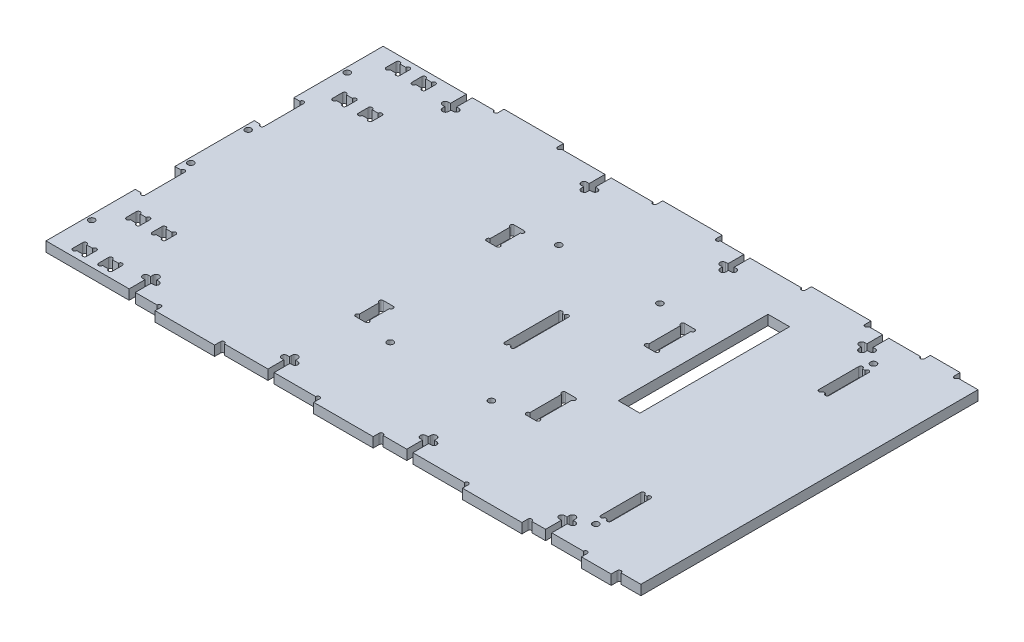
SolidWorks part; units mm, degrees
ref_plane "정면" through (0, 0, 0) normal (0, 0, 1) x (1, 0, 0)
ref_plane "윗면" through (0, 0, 0) normal (0, 1, 0) x (1, 0, 0)
ref_plane "우측면" through (0, 0, 0) normal (1, 0, 0) x (0, 0, -1)
sketch "스케치1" plane through (0, 0, 0) normal (0, 1, 0) x (1, 0, 0)
  line L1 (0, 0) -> (300, 0)
  line L2 (0, 0) -> (0, 170)
  line L3 (0, 170) -> (300, 170)
  line L4 (300, 0) -> (300, 170)
  dimension "D1" = 170
  dimension "D2" = 300
extrude "보스-돌출1" add sketch "스케치1" along normal blind 5
sketch "스케치2" plane through (0, 0, 0) normal (0, -1, 0) x (1, 0, 0)
  line L0 (159.9, -71.5) -> (159.9, 0) construction
  line L1 (159.9, -71.5) -> (165.1, -71.5)
  line L2 (159.9, -71.5) -> (159.9, -98.5)
  line L3 (159.9, -98.5) -> (165.1, -98.5)
  line L4 (165.1, -71.5) -> (165.1, -98.5)
  line L5 (0, 0) -> (300, 0) construction
  line L6 (159.9, -98.5) -> (159.9, -170) construction
  line L7 (300, -170) -> (0, -170) construction
  line L10 (300, 0) -> (300, -170) construction
  line L11 (259.8, 0) -> (259.8, -20) construction
  line L12 (259.8, -20) -> (265, -20)
  line L13 (259.8, -20) -> (259.8, -40)
  line L14 (259.8, -40) -> (265, -40)
  line L15 (265, -20) -> (265, -40)
  line L16 (259.8, -130) -> (265, -130)
  line L17 (259.8, -130) -> (259.8, -150)
  line L18 (259.8, -150) -> (265, -150)
  line L19 (265, -130) -> (265, -150)
  line L20 (259.8, -40) -> (259.8, -130) construction
  line L21 (259.8, -150) -> (259.8, -170) construction
  line L22 (265, -130) -> (265, -40) construction
  dimension "D1" = 27
  dimension "D2" = 140.1
  dimension "D3" = 5.2
  dimension "D4" = 20
  dimension "D5" = 20
  dimension "D6" = 40.2
  dimension "D7" = 5.2
extrude "컷-돌출1" cut sketch "스케치2" against normal blind 10
sketch "스케치3" plane through (0, 5, 0) normal (0, 1, 0) x (1, 0, 0)
  line L0 (183.65, 42.5) -> (180.55, 42.5) construction
  line L1 (183.65, 40) -> (183.65, 45) construction
  line L2 (180.55, 40) -> (180.55, 45) construction
  line L3 (180.55, 42.5) -> (132.65, 42.5) construction
  line L4 (132.65, 40) -> (132.65, 45) construction
  line L5 (132.65, 42.5) -> (129.55, 42.5) construction
  line L6 (129.55, 40) -> (129.55, 45) construction
  line L7 (183.65, 127.5) -> (180.55, 127.5) construction
  line L8 (183.65, 125) -> (183.65, 130) construction
  line L9 (180.55, 125) -> (180.55, 130) construction
  line L10 (180.55, 127.5) -> (132.65, 127.5) construction
  line L11 (132.65, 125) -> (132.65, 130) construction
  line L12 (132.65, 127.5) -> (129.55, 127.5) construction
  line L13 (129.55, 125) -> (129.55, 130) construction
  line L15 (2.5, 101) -> (2.5, 97.9) construction
  line L17 (5, 101) -> (0, 101) construction
  line L18 (262.3, 16.55) -> (262.3, 13.45) construction
  line L19 (264.8, 16.55) -> (259.8, 16.55) construction
  line L20 (264.8, 13.45) -> (259.8, 13.45) construction
  line L25 (262.3, 156.55) -> (262.3, 153.45) construction
  line L26 (264.8, 156.55) -> (259.8, 156.55) construction
  line L27 (264.8, 153.45) -> (259.8, 153.45) construction
  line L28 (5, 97.9) -> (0, 97.9) construction
  line L31 (2.5, 151) -> (2.5, 147.9) construction
  line L34 (2.5, 22.1) -> (2.5, 19) construction
  line L35 (5, 22.1) -> (0, 22.1) construction
  line L36 (5, 19) -> (0, 19) construction
  line L37 (2.5, 72.1) -> (2.5, 69) construction
  line L38 (5, 72.1) -> (0, 72.1) construction
  line L39 (5, 69) -> (0, 69) construction
  line L40 (5, 151) -> (0, 151) construction
  line L41 (5, 147.9) -> (0, 147.9) construction
  circle A0 centre (131.1, 127.5) radius 1.55
  circle A1 centre (182.1, 127.5) radius 1.55
  circle A2 centre (182.1, 42.5) radius 1.55
  circle A3 centre (131.1, 42.5) radius 1.55
  circle A4 centre (2.5, 70.55) radius 1.55
  circle A5 centre (2.5, 20.55) radius 1.55
  circle A6 centre (2.5, 99.45) radius 1.55
  circle A7 centre (2.5, 149.45) radius 1.55
  circle A8 centre (262.3, 155) radius 1.55
  circle A10 centre (262.3, 15) radius 1.55
  dimension "D1" = 3.1
extrude "컷-돌출2" cut sketch "스케치3" against normal blind 10
sketch "스케치4" plane through (0, 0, 0) normal (0, -1, 0) x (1, 0, 0)
  line L1 (0, -125) -> (5, -125)
  line L2 (0, -125) -> (0, -105)
  line L3 (0, -105) -> (5, -105)
  line L4 (5, -125) -> (5, -105)
  line L5 (0, -65) -> (5, -65)
  line L6 (0, -65) -> (0, -45)
  line L7 (0, -45) -> (5, -45)
  line L8 (5, -65) -> (5, -45)
extrude "컷-돌출3" cut sketch "스케치4" against normal blind 5
sketch "스케치5" plane through (0, 0, 0) normal (0, -1, 0) x (1, 0, 0)
  line L2 (5, -45) -> (0, -45) construction
  line L3 (0, -65) -> (5, -65) construction
  line L4 (5, -105) -> (0, -105) construction
  line L5 (0, -125) -> (5, -125) construction
  line L6 (159.9, -98.5) -> (165.1, -98.5) construction
  line L7 (165.1, -71.5) -> (159.9, -71.5) construction
  line L8 (265, -20) -> (259.8, -20) construction
  line L9 (259.8, -40) -> (265, -40) construction
  line L10 (265, -130) -> (259.8, -130) construction
  line L11 (259.8, -150) -> (265, -150) construction
  circle A1 centre (4, -45) radius 1
  circle A2 centre (4, -65) radius 1
  circle A5 centre (4, -105) radius 1
  circle A6 centre (4, -125) radius 1
  circle A8 centre (164.1, -98.5) radius 1
  circle A9 centre (160.9, -98.5) radius 1
  circle A10 centre (164.1, -71.5) radius 1
  circle A11 centre (160.9, -71.5) radius 1
  circle A12 centre (264, -20) radius 1
  circle A13 centre (260.8, -20) radius 1
  circle A14 centre (264, -40) radius 1
  circle A15 centre (260.8, -40) radius 1
  circle A16 centre (264, -130) radius 1
  circle A17 centre (260.8, -130) radius 1
  circle A18 centre (264, -150) radius 1
  circle A19 centre (260.8, -150) radius 1
  dimension "D1" = 2
extrude "컷-돌출4" cut sketch "스케치5" against normal blind 10
sketch "스케치8" plane through (0, 0, 0) normal (0, -1, 0) x (1, 0, 0)
  line L0 (0, 0) -> (300, 0) construction
  line L1 (58, 0) -> (88, 0)
  line L2 (58, 0) -> (58, 3)
  line L3 (58, 3) -> (88, 3)
  line L4 (88, 0) -> (88, 3)
  line L5 (0, 3) -> (58, 3) construction
  line L6 (0, 0) -> (300, 0) construction
  line L7 (138, 3) -> (168, 3)
  line L8 (138, 3) -> (138, 0)
  line L9 (138, 0) -> (168, 0)
  line L10 (168, 3) -> (168, 0)
  line L11 (0, 0) -> (300, 0) construction
  line L12 (213, 3) -> (243, 3)
  line L13 (213, 3) -> (213, 0)
  line L14 (213, 0) -> (243, 0)
  line L15 (243, 3) -> (243, 0)
  line L16 (0, 0) -> (300, 0) construction
  line L17 (273, 3) -> (288, 3)
  line L18 (273, 3) -> (273, 0)
  line L19 (273, 0) -> (288, 0)
  line L20 (288, 3) -> (288, 0)
  line L21 (300, 0) -> (300, -170) construction
  line L22 (0, -85) -> (300, -85) construction
  line L23 (0, -105) -> (0, -65) construction
  line L24 (288, -173) -> (288, -170)
  line L25 (273, -170) -> (288, -170)
  line L26 (273, -173) -> (273, -170)
  line L27 (273, -173) -> (288, -173)
  line L28 (243, -173) -> (243, -170)
  line L29 (213, -170) -> (243, -170)
  line L30 (213, -173) -> (213, -170)
  line L31 (213, -173) -> (243, -173)
  line L32 (168, -173) -> (168, -170)
  line L33 (138, -170) -> (168, -170)
  line L34 (138, -173) -> (138, -170)
  line L35 (138, -173) -> (168, -173)
  line L36 (88, -170) -> (88, -173)
  line L37 (58, -173) -> (88, -173)
  line L38 (58, -170) -> (58, -173)
  line L39 (58, -170) -> (88, -170)
  dimension "D1" = 12
  dimension "D2" = 15
  dimension "D3" = 30
  dimension "D4" = 30
  dimension "D5" = 45
  dimension "D6" = 30
  dimension "D7" = 50
  dimension "D8" = 30
extrude "보스-돌출2" add sketch "스케치8" against normal blind 5
sketch "스케치9" plane through (0, 0, 0) normal (0, -1, 0) x (1, 0, 0)
  line L0 (0, 0) -> (58, 0) construction
  line L1 (88, 0) -> (138, 0) construction
  line L2 (88, 0) -> (138, 0) construction
  line L3 (168, 0) -> (213, 0) construction
  line L4 (168, 0) -> (213, 0) construction
  line L5 (243, 0) -> (273, 0) construction
  line L6 (243, 0) -> (273, 0) construction
  line L7 (288, 0) -> (300, 0) construction
  line L8 (0, -85) -> (300, -85) construction
  line L9 (0, -105) -> (0, -65) construction
  line L10 (300, 0) -> (300, -170) construction
  circle A0 centre (57, 0) radius 1
  circle A1 centre (89, 0) radius 1
  circle A2 centre (137, 0) radius 1
  circle A3 centre (169, 0) radius 1
  circle A4 centre (212, 0) radius 1
  circle A5 centre (272, 0) radius 1
  circle A6 centre (244, 0) radius 1
  circle A7 centre (289, 0) radius 1
  circle A8 centre (289, -170) radius 1
  circle A9 centre (244, -170) radius 1
  circle A10 centre (272, -170) radius 1
  circle A11 centre (212, -170) radius 1
  circle A12 centre (169, -170) radius 1
  circle A13 centre (137, -170) radius 1
  circle A14 centre (89, -170) radius 1
  circle A15 centre (57, -170) radius 1
  dimension "D1" = 2
extrude "컷-돌출6" cut sketch "스케치9" against normal blind 5
sketch "스케치13" plane through (0, 5, 0) normal (0, 1, 0) x (1, 0, 0)
  line L0 (30, 8.5) -> (30, 30.5) construction
  line L1 (30, 8.5) -> (23, 8.5)
  line L2 (30, 8.5) -> (30, 3.5)
  line L3 (30, 3.5) -> (23, 3.5)
  line L4 (23, 8.5) -> (23, 3.5)
  line L5 (17, 8.5) -> (10, 8.5)
  line L6 (17, 8.5) -> (17, 3.5)
  line L7 (17, 3.5) -> (10, 3.5)
  line L8 (10, 8.5) -> (10, 3.5)
  line L9 (30, 19.5) -> (11.9274, 19.5) construction
  line L10 (10, 30.5) -> (10, 35.5)
  line L11 (17, 35.5) -> (10, 35.5)
  line L12 (17, 30.5) -> (17, 35.5)
  line L13 (17, 30.5) -> (10, 30.5)
  line L14 (23, 30.5) -> (23, 35.5)
  line L15 (30, 35.5) -> (23, 35.5)
  line L16 (30, 30.5) -> (30, 35.5)
  line L17 (30, 30.5) -> (23, 30.5)
  line L18 (0, 85) -> (49.672, 85) construction
  line L19 (0, 105) -> (0, 65) construction
  line L20 (30, 150.5) -> (11.9274, 150.5) construction
  line L21 (30, 161.5) -> (30, 139.5) construction
  line L22 (30, 139.5) -> (23, 139.5)
  line L23 (30, 139.5) -> (30, 134.5)
  line L24 (30, 134.5) -> (23, 134.5)
  line L25 (23, 139.5) -> (23, 134.5)
  line L26 (17, 139.5) -> (10, 139.5)
  line L27 (17, 139.5) -> (17, 134.5)
  line L28 (17, 134.5) -> (10, 134.5)
  line L29 (10, 139.5) -> (10, 134.5)
  line L30 (10, 161.5) -> (10, 166.5)
  line L31 (17, 166.5) -> (10, 166.5)
  line L32 (17, 161.5) -> (17, 166.5)
  line L33 (17, 161.5) -> (10, 161.5)
  line L34 (23, 161.5) -> (23, 166.5)
  line L35 (30, 166.5) -> (23, 166.5)
  line L36 (30, 161.5) -> (30, 166.5)
  line L37 (30, 161.5) -> (23, 161.5)
extrude "컷-돌출9" cut sketch "스케치13" against normal blind 10
sketch "스케치14" plane through (0, 0, 0) normal (0, -1, 0) x (1, 0, 0)
  line L0 (10, -8.5) -> (17, -8.5) construction
  line L1 (17, -3.5) -> (10, -3.5) construction
  line L2 (17, -30.5) -> (23, -30.5) construction
  line L3 (23, -30.5) -> (23, -8.5) construction
  line L4 (23, -8.5) -> (17, -8.5) construction
  line L5 (17, -8.5) -> (17, -30.5) construction
  line L6 (20, -30.5) -> (20, -8.5) construction
  line L7 (17, -19.5) -> (23, -19.5) construction
  line L8 (0, -85) -> (55.1733, -85) construction
  line L9 (0, -105) -> (0, -65) construction
  line L10 (17, -150.5) -> (23, -150.5) construction
  line L11 (20, -139.5) -> (20, -161.5) construction
  line L12 (17, -161.5) -> (17, -139.5) construction
  line L13 (23, -161.5) -> (17, -161.5) construction
  line L14 (23, -139.5) -> (23, -161.5) construction
  line L15 (17, -139.5) -> (23, -139.5) construction
  circle A0 centre (11, -8.5) radius 1
  circle A1 centre (11, -3.5) radius 1
  circle A2 centre (16, -3.5) radius 1
  circle A3 centre (16, -8.5) radius 1
  circle A4 centre (24, -8.5) radius 1
  circle A5 centre (24, -3.5) radius 1
  circle A6 centre (29, -3.5) radius 1
  circle A7 centre (29, -8.5) radius 1
  circle A8 centre (29, -30.5) radius 1
  circle A9 centre (29, -35.5) radius 1
  circle A10 centre (24, -35.5) radius 1
  circle A11 centre (24, -30.5) radius 1
  circle A12 centre (16, -30.5) radius 1
  circle A13 centre (16, -35.5) radius 1
  circle A14 centre (11, -35.5) radius 1
  circle A15 centre (11, -30.5) radius 1
  circle A16 centre (11, -139.5) radius 1
  circle A17 centre (11, -134.5) radius 1
  circle A18 centre (16, -134.5) radius 1
  circle A19 centre (16, -139.5) radius 1
  circle A20 centre (24, -139.5) radius 1
  circle A21 centre (24, -134.5) radius 1
  circle A22 centre (29, -134.5) radius 1
  circle A23 centre (29, -139.5) radius 1
  circle A24 centre (29, -161.5) radius 1
  circle A25 centre (29, -166.5) radius 1
  circle A26 centre (24, -166.5) radius 1
  circle A27 centre (24, -161.5) radius 1
  circle A28 centre (16, -161.5) radius 1
  circle A29 centre (16, -166.5) radius 1
  circle A30 centre (11, -166.5) radius 1
  circle A31 centre (11, -161.5) radius 1
  dimension "D1" = 2
extrude "컷-돌출10" cut sketch "스케치14" against normal blind 10
sketch "스케치15" plane through (0, 5, 0) normal (0, 1, 0) x (1, 0, 0)
  line L1 (111.1, 125) -> (116.1, 125)
  line L2 (111.1, 125) -> (111.1, 111)
  line L3 (111.1, 111) -> (116.1, 111)
  line L4 (116.1, 125) -> (116.1, 111)
  line L5 (111.1, 45) -> (116.1, 45)
  line L6 (111.1, 45) -> (111.1, 59)
  line L7 (111.1, 59) -> (116.1, 59)
  line L8 (116.1, 45) -> (116.1, 59)
  line L9 (197.1, 65) -> (202.1, 65)
  line L10 (197.1, 65) -> (197.1, 45)
  line L11 (197.1, 45) -> (202.1, 45)
  line L12 (202.1, 65) -> (202.1, 45)
  line L13 (197.1, 105) -> (202.1, 105)
  line L14 (197.1, 105) -> (197.1, 125)
  line L15 (197.1, 125) -> (202.1, 125)
  line L16 (202.1, 105) -> (202.1, 125)
  arc A0 (116.1, 56.5) -> (116.1, 59) centre (116.1, 57.75) ccw construction
  dimension "D1" = 5
extrude "컷-돌출11" cut sketch "스케치15" against normal blind 10
sketch "스케치16" plane through (0, 5, 0) normal (0, 1, 0) x (1, 0, 0)
  line L0 (111.1, 59) -> (111.1, 45) construction
  line L1 (116.1, 45) -> (116.1, 59) construction
  line L2 (111.1, 125) -> (111.1, 111) construction
  line L3 (116.1, 111) -> (116.1, 125) construction
  line L4 (202.1, 105) -> (202.1, 125) construction
  line L5 (197.1, 125) -> (197.1, 105) construction
  line L6 (197.1, 65) -> (197.1, 45) construction
  line L7 (202.1, 45) -> (202.1, 65) construction
  circle A0 centre (111.1, 46) radius 1
  circle A1 centre (116.1, 46) radius 1
  circle A2 centre (116.1, 58) radius 1
  circle A3 centre (111.1, 58) radius 1
  circle A4 centre (111.1, 112) radius 1
  circle A5 centre (116.1, 112) radius 1
  circle A6 centre (116.1, 124) radius 1
  circle A7 centre (111.1, 124) radius 1
  circle A8 centre (202.1, 124) radius 1
  circle A10 centre (197.1, 124) radius 1
  circle A11 centre (197.1, 64) radius 1
  circle A12 centre (202.1, 64) radius 1
  circle A13 centre (202.1, 106) radius 1
  circle A14 centre (197.1, 106) radius 1
  circle A15 centre (197.1, 46) radius 1
  circle A16 centre (202.1, 46) radius 1
  dimension "D1" = 2
extrude "컷-돌출12" cut sketch "스케치16" against normal blind 10
sketch "스케치17" plane through (0, 5, 0) normal (0, 1, 0) x (1, 0, 0)
  line L0 (219.1, 97.5569) -> (219.1, 95.1974) construction
  line L1 (214.1, 74.5) -> (225, 74.5)
  line L2 (214.1, 74.5) -> (214.1, 150)
  line L3 (214.1, 150) -> (225, 150)
  line L4 (225, 74.5) -> (225, 150)
  line L6 (220, 97.5569) -> (220, 95.1974) construction
  line L7 (2.5, -5.5) -> (297.5, -5.5) construction
  line L8 (211, 170) -> (170, 170) construction
  dimension "D1" = 5
  dimension "D2" = 5
  dimension "D3" = 80
  dimension "D4" = 20
extrude "컷-돌출13" cut sketch "스케치17" against normal blind 10
sketch "스케치7" plane through (0, 0, 0) normal (0, -1, 0) x (1, 0, 0)
  line L0 (115.0287, -170) -> (111.9287, -170)
  line L1 (115.0287, -162) -> (116.2287, -162)
  line L2 (115.0287, -159.2) -> (115.0287, -158)
  line L3 (111.9287, -159.2) -> (111.9287, -158)
  line L4 (111.9287, -159.2) -> (110.7287, -159.2)
  line L5 (111.9287, -170) -> (111.9287, -162)
  line L6 (110.7287, -162) -> (111.9287, -162)
  line L7 (115.0287, -170) -> (115.0287, -162)
  line L8 (116.2287, -159.2) -> (115.0287, -159.2)
  line L9 (115.0287, -159.2) -> (111.9287, -159.2) construction
  line L10 (115.0287, -159.2) -> (115.0287, -162) construction
  line L11 (111.9287, -162) -> (111.9287, -159.2) construction
  line L12 (115.0287, -158) -> (111.9287, -158) construction
  line L13 (113.4787, -158) -> (113.4787, -155.529) construction
  line L14 (110.7287, -159.2) -> (110.7287, -162) construction
  line L15 (116.2287, -162) -> (116.2287, -159.2) construction
  line L16 (115.0287, -162) -> (111.9287, -162) construction
  line L17 (185.0287, -170) -> (181.9287, -170)
  line L18 (185.0287, -162) -> (186.2287, -162)
  line L19 (185.0287, -159.2) -> (185.0287, -158)
  line L20 (181.9287, -159.2) -> (181.9287, -158)
  line L21 (181.9287, -159.2) -> (180.7287, -159.2)
  line L22 (181.9287, -170) -> (181.9287, -162)
  line L23 (180.7287, -162) -> (181.9287, -162)
  line L24 (185.0287, -170) -> (185.0287, -162)
  line L25 (186.2287, -159.2) -> (185.0287, -159.2)
  line L26 (185.0287, -159.2) -> (181.9287, -159.2) construction
  line L27 (185.0287, -159.2) -> (185.0287, -162) construction
  line L28 (181.9287, -162) -> (181.9287, -159.2) construction
  line L29 (185.0287, -158) -> (181.9287, -158) construction
  line L30 (45.0287, -159.2) -> (41.9287, -159.2) construction
  line L31 (45.0287, -159.2) -> (45.0287, -162) construction
  line L32 (41.9287, -162) -> (41.9287, -159.2) construction
  line L33 (45.0287, -158) -> (41.9287, -158) construction
  line L34 (43.4787, -158) -> (43.4787, -155.529) construction
  line L35 (183.4787, -158) -> (183.4787, -155.529) construction
  line L36 (180.7287, -159.2) -> (180.7287, -162) construction
  line L37 (186.2287, -162) -> (186.2287, -159.2) construction
  line L38 (185.0287, -162) -> (181.9287, -162) construction
  line L39 (255.0287, -170) -> (251.9287, -170)
  line L40 (255.0287, -162) -> (256.2287, -162)
  line L41 (255.0287, -159.2) -> (255.0287, -158)
  line L42 (251.9287, -159.2) -> (251.9287, -158)
  line L43 (251.9287, -159.2) -> (250.7287, -159.2)
  line L44 (251.9287, -170) -> (251.9287, -162)
  line L45 (250.7287, -162) -> (251.9287, -162)
  line L46 (255.0287, -170) -> (255.0287, -162)
  line L47 (256.2287, -159.2) -> (255.0287, -159.2)
  line L48 (255.0287, -159.2) -> (251.9287, -159.2) construction
  line L49 (255.0287, -159.2) -> (255.0287, -162) construction
  line L50 (251.9287, -162) -> (251.9287, -159.2) construction
  line L51 (255.0287, -158) -> (251.9287, -158) construction
  line L52 (253.4787, -158) -> (253.4787, -155.529) construction
  line L53 (250.7287, -159.2) -> (250.7287, -162) construction
  line L54 (256.2287, -162) -> (256.2287, -159.2) construction
  line L55 (255.0287, -162) -> (251.9287, -162) construction
  line L56 (45.0287, -8) -> (41.9287, -8) construction
  line L57 (46.2287, -8) -> (46.2287, -10.8) construction
  line L58 (40.7287, -10.8) -> (40.7287, -8) construction
  line L59 (255.0287, -8) -> (251.9287, -8) construction
  line L60 (256.2287, -8) -> (256.2287, -10.8) construction
  line L61 (250.7287, -10.8) -> (250.7287, -8) construction
  line L62 (253.4787, -12) -> (253.4787, -14.471) construction
  line L63 (255.0287, -12) -> (251.9287, -12) construction
  line L64 (251.9287, -8) -> (251.9287, -10.8) construction
  line L65 (255.0287, -10.8) -> (255.0287, -8) construction
  line L66 (255.0287, -10.8) -> (251.9287, -10.8) construction
  line L67 (185.0287, -8) -> (181.9287, -8) construction
  line L68 (186.2287, -8) -> (186.2287, -10.8) construction
  line L69 (40.7287, -159.2) -> (40.7287, -162) construction
  line L71 (180.7287, -10.8) -> (180.7287, -8) construction
  line L72 (183.4787, -12) -> (183.4787, -14.471) construction
  line L73 (43.4787, -12) -> (43.4787, -14.471) construction
  line L74 (45.0287, -12) -> (41.9287, -12) construction
  line L75 (0, -85) -> (300, -85) construction
  line L76 (0, -105) -> (0, -65) construction
  line L77 (300, 0) -> (300, -170) construction
  line L78 (46.2287, -162) -> (46.2287, -159.2) construction
  line L79 (45.0287, -162) -> (41.9287, -162) construction
  line L80 (41.9287, -8) -> (41.9287, -10.8) construction
  line L81 (45.0287, -10.8) -> (45.0287, -8) construction
  line L82 (45.0287, -10.8) -> (41.9287, -10.8) construction
  line L83 (185.0287, -12) -> (181.9287, -12) construction
  line L84 (181.9287, -8) -> (181.9287, -10.8) construction
  line L85 (185.0287, -10.8) -> (185.0287, -8) construction
  line L86 (185.0287, -10.8) -> (181.9287, -10.8) construction
  line L87 (115.0287, -8) -> (111.9287, -8) construction
  line L88 (116.2287, -8) -> (116.2287, -10.8) construction
  line L89 (110.7287, -10.8) -> (110.7287, -8) construction
  line L90 (113.4787, -12) -> (113.4787, -14.471) construction
  line L91 (115.0287, -12) -> (111.9287, -12) construction
  line L92 (111.9287, -8) -> (111.9287, -10.8) construction
  line L93 (115.0287, -10.8) -> (115.0287, -8) construction
  line L94 (115.0287, -10.8) -> (111.9287, -10.8) construction
  line L95 (46.2287, -10.8) -> (45.0287, -10.8)
  line L96 (45.0287, 0) -> (45.0287, -8)
  line L97 (45.0287, -170) -> (41.9287, -170)
  line L98 (45.0287, -162) -> (46.2287, -162)
  line L99 (45.0287, -159.2) -> (45.0287, -158)
  line L100 (41.9287, -159.2) -> (41.9287, -158)
  line L101 (41.9287, -159.2) -> (40.7287, -159.2)
  line L102 (41.9287, -170) -> (41.9287, -162)
  line L103 (40.7287, -162) -> (41.9287, -162)
  line L104 (45.0287, -170) -> (45.0287, -162)
  line L105 (46.2287, -159.2) -> (45.0287, -159.2)
  line L106 (325.0287, -170) -> (321.9287, -170) [skipped]
  line L107 (325.0287, -162) -> (326.2287, -162) [skipped]
  line L108 (325.0287, -159.2) -> (325.0287, -158) [skipped]
  line L109 (321.9287, -159.2) -> (321.9287, -158) [skipped]
  line L110 (321.9287, -159.2) -> (320.7287, -159.2) [skipped]
  line L111 (321.9287, -170) -> (321.9287, -162) [skipped]
  line L112 (320.7287, -162) -> (321.9287, -162) [skipped]
  line L113 (325.0287, -170) -> (325.0287, -162) [skipped]
  line L114 (326.2287, -159.2) -> (325.0287, -159.2) [skipped]
  line L115 (325.0287, -159.2) -> (321.9287, -159.2) construction
  line L116 (325.0287, -159.2) -> (325.0287, -162) construction
  line L117 (321.9287, -162) -> (321.9287, -159.2) construction
  line L118 (325.0287, -158) -> (321.9287, -158) construction
  line L119 (323.4787, -158) -> (323.4787, -155.529) construction
  line L120 (320.7287, -159.2) -> (320.7287, -162) construction
  line L121 (326.2287, -162) -> (326.2287, -159.2) construction
  line L122 (325.0287, -162) -> (321.9287, -162) construction
  line L123 (40.7287, -8) -> (41.9287, -8)
  line L124 (41.9287, 0) -> (41.9287, -8)
  line L125 (41.9287, -10.8) -> (40.7287, -10.8)
  line L126 (41.9287, -10.8) -> (41.9287, -12)
  line L127 (45.0287, -10.8) -> (45.0287, -12)
  line L128 (45.0287, -8) -> (46.2287, -8)
  line L129 (45.0287, 0) -> (41.9287, 0)
  line L130 (256.2287, -10.8) -> (255.0287, -10.8)
  line L131 (255.0287, 0) -> (255.0287, -8)
  line L132 (250.7287, -8) -> (251.9287, -8)
  line L133 (251.9287, 0) -> (251.9287, -8)
  line L134 (251.9287, -10.8) -> (250.7287, -10.8)
  line L135 (251.9287, -10.8) -> (251.9287, -12)
  line L136 (255.0287, -10.8) -> (255.0287, -12)
  line L137 (255.0287, -8) -> (256.2287, -8)
  line L138 (255.0287, 0) -> (251.9287, 0)
  line L139 (186.2287, -10.8) -> (185.0287, -10.8)
  line L140 (185.0287, 0) -> (185.0287, -8)
  line L141 (180.7287, -8) -> (181.9287, -8)
  line L142 (181.9287, 0) -> (181.9287, -8)
  line L143 (181.9287, -10.8) -> (180.7287, -10.8)
  line L144 (181.9287, -10.8) -> (181.9287, -12)
  line L145 (185.0287, -10.8) -> (185.0287, -12)
  line L146 (185.0287, -8) -> (186.2287, -8)
  line L147 (185.0287, 0) -> (181.9287, 0)
  line L148 (116.2287, -10.8) -> (115.0287, -10.8)
  line L149 (115.0287, 0) -> (115.0287, -8)
  line L150 (110.7287, -8) -> (111.9287, -8)
  line L151 (111.9287, 0) -> (111.9287, -8)
  line L152 (111.9287, -10.8) -> (110.7287, -10.8)
  line L153 (111.9287, -10.8) -> (111.9287, -12)
  line L154 (115.0287, -10.8) -> (115.0287, -12)
  line L155 (115.0287, -8) -> (116.2287, -8)
  line L156 (115.0287, 0) -> (111.9287, 0)
  arc A0 (111.9287, -158) -> (115.0287, -158) centre (113.4787, -158) cw
  arc A1 (116.2287, -159.2) -> (116.2287, -162) centre (116.2287, -160.6) cw
  arc A2 (110.7287, -162) -> (110.7287, -159.2) centre (110.7287, -160.6) cw
  arc A3 (181.9287, -158) -> (185.0287, -158) centre (183.4787, -158) cw
  arc A4 (186.2287, -159.2) -> (186.2287, -162) centre (186.2287, -160.6) cw
  arc A5 (180.7287, -162) -> (180.7287, -159.2) centre (180.7287, -160.6) cw
  arc A6 (251.9287, -158) -> (255.0287, -158) centre (253.4787, -158) cw
  arc A7 (256.2287, -159.2) -> (256.2287, -162) centre (256.2287, -160.6) cw
  arc A8 (250.7287, -162) -> (250.7287, -159.2) centre (250.7287, -160.6) cw
  arc A9 (40.7287, -8) -> (40.7287, -10.8) centre (40.7287, -9.4) ccw
  arc A10 (46.2287, -10.8) -> (46.2287, -8) centre (46.2287, -9.4) ccw
  arc A11 (41.9287, -12) -> (45.0287, -12) centre (43.4787, -12) ccw
  arc A12 (250.7287, -8) -> (250.7287, -10.8) centre (250.7287, -9.4) ccw
  arc A13 (41.9287, -158) -> (45.0287, -158) centre (43.4787, -158) cw
  arc A14 (46.2287, -159.2) -> (46.2287, -162) centre (46.2287, -160.6) cw
  arc A15 (40.7287, -162) -> (40.7287, -159.2) centre (40.7287, -160.6) cw
  arc A16 (321.9287, -158) -> (325.0287, -158) centre (323.4787, -158) cw [skipped]
  arc A17 (326.2287, -159.2) -> (326.2287, -162) centre (326.2287, -160.6) cw [skipped]
  arc A18 (320.7287, -162) -> (320.7287, -159.2) centre (320.7287, -160.6) cw [skipped]
  arc A19 (256.2287, -10.8) -> (256.2287, -8) centre (256.2287, -9.4) ccw
  arc A20 (251.9287, -12) -> (255.0287, -12) centre (253.4787, -12) ccw
  arc A21 (180.7287, -8) -> (180.7287, -10.8) centre (180.7287, -9.4) ccw
  arc A22 (186.2287, -10.8) -> (186.2287, -8) centre (186.2287, -9.4) ccw
  arc A23 (181.9287, -12) -> (185.0287, -12) centre (183.4787, -12) ccw
  arc A24 (110.7287, -8) -> (110.7287, -10.8) centre (110.7287, -9.4) ccw
  arc A25 (116.2287, -10.8) -> (116.2287, -8) centre (116.2287, -9.4) ccw
  arc A26 (111.9287, -12) -> (115.0287, -12) centre (113.4787, -12) ccw
  dimension "D1" = 5
  dimension "D2" = 8
extrude "컷-돌출5" cut sketch "스케치7" against normal blind 10
sketch "스케치18" plane through (0, 0, 0) normal (0, -1, 0) x (1, 0, 0)
  line L0 (0, -85) -> (300, -85) construction
  line L1 (0, -105) -> (0, -65) construction
  line L2 (300, 0) -> (300, -170) construction
  line L4 (285, -152.5) -> (15, -152.5) construction
  line L5 (285, -152.5) -> (285, -17.5) construction
  line L6 (285, -17.5) -> (15, -17.5) construction
  line L7 (15, -152.5) -> (15, -17.5) construction
  line L8 (285, -152.5) -> (15, -17.5) construction
  line L9 (285, -17.5) -> (15, -152.5) construction
  circle A0 centre (15, -17.5) radius 6
  circle A1 centre (15, -152.5) radius 6
  circle A2 centre (285, -17.5) radius 6
  circle A3 centre (285, -152.5) radius 6
  point P6 (150, -85)
  dimension "D3" = 12
  dimension "D1" = 135
  dimension "D2" = 270
extrude "컷-돌출14" cut sketch "스케치18" against normal blind 1.5
sketch "스케치19" plane through (0, 5, 0) normal (0, 1, 0) x (1, 0, 0)
  line L0 (111.1, 123) -> (111.1, 113) construction
  line L1 (111, 123.914) -> (116.2, 123.914)
  line L2 (111, 123.914) -> (111, 112.1352)
  line L3 (111, 112.1352) -> (116.2, 112.1352)
  line L4 (116.2, 123.914) -> (116.2, 112.1352)
  line L5 (111, 57.988) -> (116.2, 57.988)
  line L6 (111, 57.988) -> (111, 46.2932)
  line L7 (111, 46.2932) -> (116.2, 46.2932)
  line L8 (116.2, 57.988) -> (116.2, 46.2932)
  line L9 (197, 63.9937) -> (202.2, 63.9937)
  line L10 (197, 63.9937) -> (197, 46.6181)
  line L11 (197, 46.6181) -> (202.2, 46.6181)
  line L12 (202.2, 63.9937) -> (202.2, 46.6181)
  line L13 (197, 123.914) -> (202.2, 123.914)
  line L14 (197, 123.914) -> (197, 106.2522)
  line L15 (197, 106.2522) -> (202.2, 106.2522)
  line L16 (202.2, 123.914) -> (202.2, 106.2522)
  line L17 (116.1, 113) -> (116.1, 123) construction
  line L18 (111.1, 57) -> (111.1, 47) construction
  line L19 (116.1, 47) -> (116.1, 57) construction
  line L20 (197.1, 63) -> (197.1, 47) construction
  line L21 (202.1, 47) -> (202.1, 63) construction
  line L22 (197.1, 123) -> (197.1, 107) construction
  line L23 (202.1, 107) -> (202.1, 123) construction
  dimension "D1" = 0.1
  dimension "D2" = 0.1
  dimension "D3" = 0.1
  dimension "D4" = 0.1
  dimension "D5" = 0.1
  dimension "D6" = 0.1
  dimension "D7" = 0.1
  dimension "D8" = 0.1
extrude "컷-돌출15" cut sketch "스케치19" against normal blind 10
